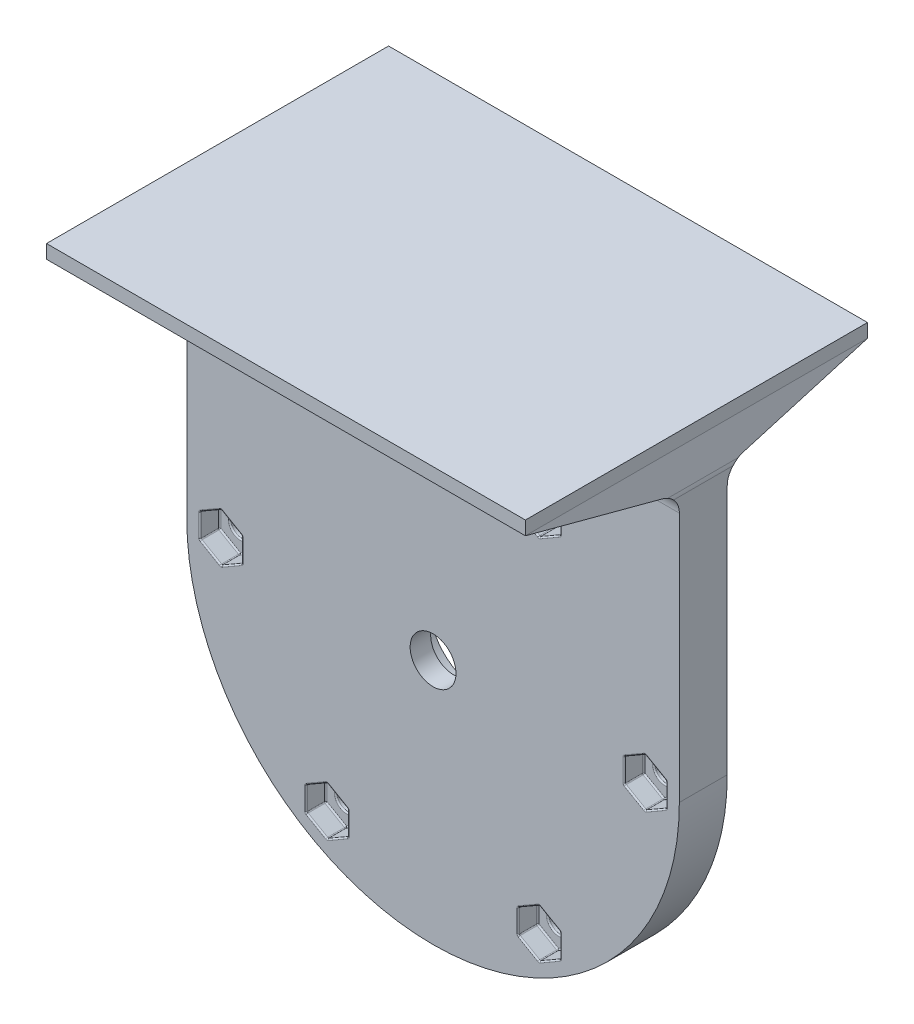
SolidWorks part; units mm, degrees
ref_plane "Front Plane" through (0, 0, 0) normal (0, 0, 1) x (1, 0, 0)
ref_plane "Top Plane" through (0, 0, 0) normal (0, 1, 0) x (1, 0, 0)
ref_plane "Right Plane" through (0, 0, 0) normal (1, 0, 0) x (0, 0, -1)
sketch "Sketch1" plane through (0, 0, 0) normal (0, 0, 1) x (1, 0, 0)
  circle A2 centre (0, 0) radius 36
  circle A3 centre (0, 0) radius 3.35
  dimension "D1" = 72
  dimension "D2" = 6.7
extrude "Boss-Extrude1" add sketch "Sketch1" along normal mid plane 7
sketch "Sketch2" plane through (0, 0, 0) normal (0, 0, 1) x (1, 0, 0)
  line L0 (-34.048, 0) -> (0, 0) construction
  line L37 (-27.952, -1.7598) -> (-27.952, 1.7598)
  line L38 (-27.952, 1.7598) -> (-31, 3.5195)
  line L39 (-31, 3.5195) -> (-34.048, 1.7598)
  line L40 (-34.048, 1.7598) -> (-34.048, -1.7598)
  line L41 (-34.048, -1.7598) -> (-31, -3.5195)
  line L42 (-31, -3.5195) -> (-27.952, -1.7598)
  circle A1 centre (0, 0) radius 31 construction
  circle A2 centre (-31, 0) radius 3.048 construction
  dimension "D1" = 6.096
  dimension "D2" = 62
extrude "Cut-Extrude1" cut sketch "Sketch2" against normal blind 2.8575 from surface starting at face at (36, 0, 3.5)
sketch "Sketch3" plane through (0, 0, 0) normal (0, 0, -1) x (-1, 0, 0)
  line L0 (31, 3.5195) -> (31, -3.5195) construction
  circle A1 centre (31, 0) radius 1.5875
  dimension "D1" = 3.175
extrude "Cut-Extrude2" cut sketch "Sketch3" along normal up to next from surface starting at face at (-31, 0, 0.6425)
fillet "Fillet2" radius 0.2 20 edges at (-29.476, -2.6396, 3.5) (-29.476, 2.6396, 3.5) (-34.048, 0, 3.5) (-34.048, -1.7598, 2.0713) (-31, -3.5195, 2.0713) (-32.524, -2.6396, 3.5) (-27.952, -1.7598, 2.0713) (-27.952, 1.7598, 2.0713) (-27.952, 0, 3.5) (-31, 3.5195, 2.0713) (-34.048, 1.7598, 2.0713) (-32.524, 2.6396, 3.5) (-32.524, 2.6396, 0.6425) (-29.476, 2.6396, 0.6425) (-27.952, 0, 0.6425) (-29.476, -2.6396, 0.6425) (-32.524, -2.6396, 0.6425) (-34.048, 0, 0.6425) (-32.5875, 0, 0.6425) (-29.4125, 0, -3.5)
pattern_circular "CirPattern1" count 6 over 360 about axis through (0, 0, 3.5) along (0, 0, -1) of "Cut-Extrude1", "Cut-Extrude2", "Fillet2"
ref_plane "Plane1" through (0, 39, 0) normal (0, 1, 0) x (1, 0, 0)
sketch "Sketch5" plane through (0, 39, 0) normal (0, 1, 0) x (1, 0, 0)
  line L1 (-36, 3.5) -> (36, 3.5)
  line L2 (-36, 3.5) -> (-36, -3.5)
  line L3 (-36, -3.5) -> (36, -3.5)
  line L4 (36, 3.5) -> (36, -3.5)
extrude "Boss-Extrude2" add sketch "Sketch5" against normal up to surface (39 mm away) up to face at (36, 0, 3.5)
ref_plane "Plane2" through (0, 44, 0) normal (0, 1, 0) x (1, 0, 0)
sketch "Sketch6" plane through (0, 44, 0) normal (0, 1, 0) x (1, 0, 0)
  line L0 (-35, 0) -> (35, 0) construction
  line L1 (-35, 25) -> (35, 25)
  line L2 (-35, 25) -> (-35, -25)
  line L3 (-35, -25) -> (35, -25)
  line L4 (35, 25) -> (35, -25)
  line L5 (0, 25) -> (0, -25) construction
  dimension "D1" = 70
  dimension "D2" = 50
sketch "Sketch7" plane through (0, 39, 0) normal (0, 1, 0) x (1, 0, 0)
  line L1 (-36, 3.5) -> (36, 3.5)
  line L2 (-36, 3.5) -> (-36, -3.5)
  line L3 (-36, -3.5) -> (36, -3.5)
  line L4 (36, 3.5) -> (36, -3.5)
loft "Loft1" add profiles "Sketch6", "Sketch7" connector at (35, 44, -25) connector at (36, 39, -3.5)
sketch "Sketch8" plane through (0, 44, 0) normal (0, 1, 0) x (1, 0, 0)
  line L1 (-35, 25) -> (35, 25)
  line L2 (-35, 25) -> (-35, -25)
  line L3 (-35, -25) -> (35, -25)
  line L4 (35, 25) -> (35, -25)
extrude "Boss-Extrude3" add sketch "Sketch8" along normal blind 2
sketch "Sketch9" plane through (0, 0, -3.5) normal (0, 0, -1) x (-1, 0, 0)
  circle A0 centre (0, 0) radius 7.6
  point P3 (0, 0)
  dimension "D1" = 15.2
extrude "Cut-Extrude3" cut sketch "Sketch9" against normal blind 4
fillet "Fillet6" radius 3 4 edges
